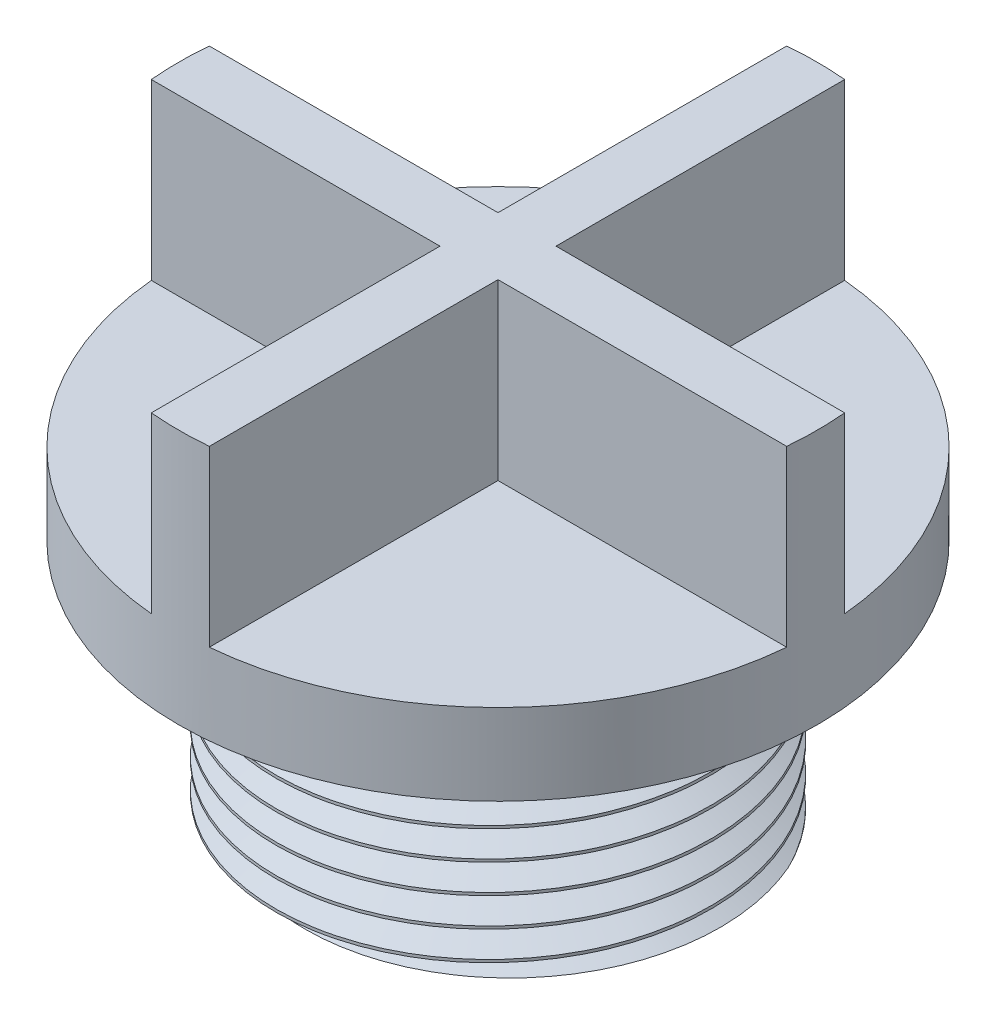
SolidWorks part; units mm, degrees
ref_plane "Front" through (0, 0, 0) normal (0, 0, 1) x (1, 0, 0)
ref_plane "Top" through (0, 0, 0) normal (0, 1, 0) x (1, 0, 0)
ref_plane "Right" through (0, 0, 0) normal (1, 0, 0) x (0, 0, -1)
sketch "Sketch1" plane through (0, 0, 0) normal (0, 1, 0) x (1, 0, 0)
  circle A0 centre (0, 0) radius 18.75
  dimension "D1" = 37.5
extrude "Boss-Extrude1" add sketch "Sketch1" along normal blind 20
sketch "Sketch2" plane through (0, 20, 0) normal (0, 1, 0) x (1, 0, 0)
  circle A0 centre (0, 0) radius 27.5
  dimension "D1" = 55
extrude "Boss-Extrude2" add sketch "Sketch2" along normal blind 7
sketch "Sketch3" plane through (0, 27, 0) normal (0, 1, 0) x (1, 0, 0)
  line L0 (0, 0) -> (0, 27.5) construction
  line L1 (0, 0) -> (27.5, 0) construction
  line L2 (2.5, 2.5) -> (27.3861, 2.5)
  line L4 (-2.5, 27.3861) -> (-2.5, 2.5)
  line L6 (2.5, 27.3861) -> (2.5, 2.5)
  line L7 (-27.3861, 2.5) -> (-2.5, 2.5)
  line L9 (-27.3861, -2.5) -> (-2.5, -2.5)
  line L11 (-2.5, -2.5) -> (-2.5, -27.3861)
  line L12 (2.5, -2.5) -> (2.5, -27.3861)
  line L13 (2.5, -2.5) -> (27.3861, -2.5)
  circle A0 centre (0, 0) radius 27.5 construction
  arc A1 (2.5, 27.3861) -> (-2.5, 27.3861) centre (0, 0) ccw
  circle A2 centre (0, 0) radius 27.5
  arc A3 (-27.3861, 2.5) -> (-27.3861, -2.5) centre (0, 0) ccw
  arc A4 (-2.5, -27.3861) -> (2.5, -27.3861) centre (0, 0) ccw
  arc A5 (27.3861, -2.5) -> (27.3861, 2.5) centre (0, 0) ccw
  dimension "D3" = 0
extrude "Boss-Extrude3" add sketch "Sketch3" along normal blind 15
sketch "Sketch4" plane through (0, 0, 0) normal (0, -1, 0) x (1, 0, 0)
  circle A0 centre (0, 0) radius 18.75 construction
  circle A1 centre (0, 0) radius 18.75
curve "Helix/Spiral1" pitch 2.5 height 18.75 radius 18.75 centre (0, 0, 0) axis (0, 1, 0) start towards (0, 0, -1)
ref_plane "Plane1" through (-13.2583, 0, 13.2583) normal (0.7069, 0.0212, 0.7069) x (0.7073, -0.0212, -0.7066)
sketch "Sketch5" plane through (-13.2583, 0, 13.2583) normal (0.7069, 0.0212, 0.7069) x (0.7073, -0.0212, -0.7066)
  line L1 (1.9537, 0) -> (-0.194, 1.24)
  line L2 (-0.194, 1.24) -> (-0.194, -1.24)
  line L3 (-0.194, -1.24) -> (1.9537, 0)
  circle A0 centre (0.5219, 0) radius 0.7159 construction
  point P1 (0.5219, 0)
  dimension "D1" = 2.48
sweep "Cut-Sweep1" cut profiles "Sketch5" path "Helix/Spiral1" align with end faces yes
